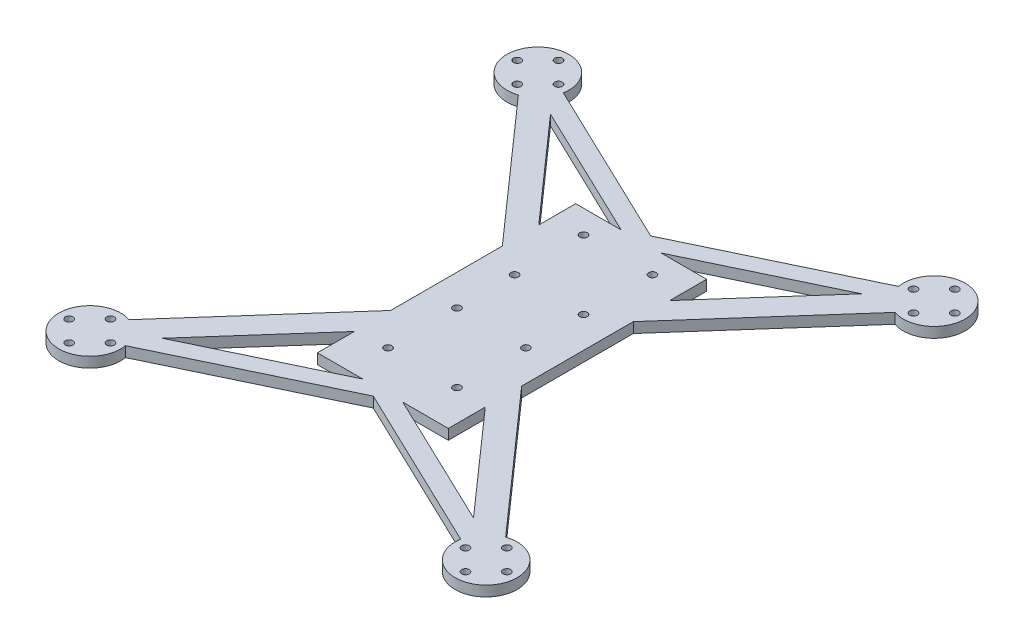
SolidWorks part; units mm, degrees
ref_plane "Front Plane" through (0, 0, 0) normal (0, 0, 1) x (1, 0, 0)
ref_plane "Top Plane" through (0, 0, 0) normal (0, 1, 0) x (1, 0, 0)
ref_plane "Right Plane" through (0, 0, 0) normal (1, 0, 0) x (0, 0, -1)
sketch "Sketch1" plane through (0, 0, 0) normal (0, 1, 0) x (1, 0, 0)
  line L0 (0, 37.475) -> (0, -37.475) construction
  line L1 (19, 37.475) -> (-19, 37.475)
  line L2 (19, 37.475) -> (19, -37.475)
  line L3 (19, -37.475) -> (-19, -37.475)
  line L4 (-19, 37.475) -> (-19, -37.475)
  line L5 (19, 37.475) -> (-19, -37.475) construction
  line L6 (19, -37.475) -> (-19, 37.475) construction
  line L7 (-19, 16.1958) -> (-54.6277, 56.4706)
  line L8 (57.5, -65) -> (-57.5, -65)
  line L9 (57.5, -65) -> (57.5, 65)
  line L10 (57.5, 65) -> (-57.5, 65)
  line L11 (-57.5, -65) -> (-57.5, 65)
  line L12 (57.5, -65) -> (-57.5, 65) construction
  line L13 (57.5, 65) -> (-57.5, -65) construction
  line L14 (-19, 16.1958) -> (-13.757, 20.8338)
  line L15 (-54.6277, 56.4706) -> (-49.3847, 61.1087)
  line L16 (-13.757, 20.8338) -> (-49.3847, 61.1087)
  line L17 (-19, 16.1958) -> (-49.3847, 61.1087) construction
  line L18 (-54.6277, 56.4706) -> (-13.757, 20.8338) construction
  line L19 (-57.5, 65) -> (0, 37.475) construction
  line L20 (-10, 30.75) -> (10, 30.75)
  line L21 (-10, 30.75) -> (-10, 10.75)
  line L22 (-10, 10.75) -> (10, 10.75)
  line L23 (10, 30.75) -> (10, 10.75)
  line L24 (-10, 30.75) -> (10, 10.75) construction
  line L25 (-10, 10.75) -> (10, 30.75) construction
  line L26 (-14.5, 5.525) -> (14.5, 5.525)
  line L27 (-14.5, 5.525) -> (-14.5, 35.975)
  line L28 (-14.5, 35.975) -> (14.5, 35.975)
  line L29 (14.5, 5.525) -> (14.5, 35.975)
  line L30 (-14.5, 5.525) -> (14.5, 35.975) construction
  line L31 (-14.5, 35.975) -> (14.5, 5.525) construction
  line L32 (-10, -5.975) -> (10, -5.975)
  line L33 (-10, -5.975) -> (-10, -25.975)
  line L34 (-10, -25.975) -> (10, -25.975)
  line L35 (10, -5.975) -> (10, -25.975)
  line L36 (-10, -5.975) -> (10, -25.975) construction
  line L37 (-10, -25.975) -> (10, -5.975) construction
  line L38 (-15.75, -35.975) -> (15.75, -35.975)
  line L39 (-15.75, -35.975) -> (-15.75, 4.025)
  line L40 (-15.75, 4.025) -> (15.75, 4.025)
  line L41 (15.75, -35.975) -> (15.75, 4.025)
  line L42 (-15.75, -35.975) -> (15.75, 4.025) construction
  line L43 (-15.75, 4.025) -> (15.75, -35.975) construction
  line L44 (-50.7811, 59.012) -> (3.6312, 32.9651)
  line L45 (-50.7811, 59.012) -> (-48.6222, 63.5219)
  line L46 (3.6312, 32.9651) -> (5.7901, 37.475)
  line L47 (-48.6222, 63.5219) -> (5.7901, 37.475)
  line L48 (-50.7811, 59.012) -> (5.7901, 37.475) construction
  line L49 (3.6312, 32.9651) -> (-48.6222, 63.5219) construction
  line L50 (50.7811, 59.012) -> (48.6222, 63.5219)
  line L51 (48.6222, 63.5219) -> (-5.7901, 37.475)
  line L52 (-3.6312, 32.9651) -> (-5.7901, 37.475)
  line L53 (50.7811, 59.012) -> (-3.6312, 32.9651)
  line L54 (19, 16.1958) -> (13.757, 20.8338)
  line L55 (13.757, 20.8338) -> (49.3847, 61.1087)
  line L56 (54.6277, 56.4706) -> (49.3847, 61.1087)
  line L57 (19, 16.1958) -> (54.6277, 56.4706)
  line L58 (-57.5, 0) -> (57.5, 0) construction
  line L64 (19, -16.1958) -> (13.757, -20.8338)
  line L65 (13.757, -20.8338) -> (49.3847, -61.1087)
  line L69 (50.7811, -59.012) -> (48.6222, -63.5219)
  line L70 (48.6222, -63.5219) -> (-5.7901, -37.475)
  line L71 (-3.6312, -32.9651) -> (-5.7901, -37.475)
  line L72 (50.7811, -59.012) -> (-3.6312, -32.9651)
  line L73 (-50.7811, -59.012) -> (-48.6222, -63.5219)
  line L74 (-48.6222, -63.5219) -> (5.7901, -37.475)
  line L75 (3.6312, -32.9651) -> (5.7901, -37.475)
  line L76 (-50.7811, -59.012) -> (3.6312, -32.9651)
  line L77 (54.6277, -56.4706) -> (49.3847, -61.1087)
  line L78 (19, -16.1958) -> (54.6277, -56.4706)
  line L79 (-19, -16.1958) -> (-13.757, -20.8338)
  line L80 (-13.757, -20.8338) -> (-49.3847, -61.1087)
  line L81 (-54.6277, -56.4706) -> (-49.3847, -61.1087)
  line L82 (-19, -16.1958) -> (-54.6277, -56.4706)
  circle A0 centre (-57.5, 65) radius 36
  circle A1 centre (-57.5, 65) radius 6
  circle A2 centre (-57.5, 65) radius 9
  circle A3 centre (-10, 30.75) radius 1.1
  circle A4 centre (10, 30.75) radius 1.1
  circle A5 centre (10, 10.75) radius 1.1
  circle A6 centre (-10, 10.75) radius 1.1
  circle A7 centre (-10, -5.975) radius 1.1
  circle A8 centre (10, -5.975) radius 1.1
  circle A9 centre (10, -25.975) radius 1.1
  circle A10 centre (-10, -25.975) radius 1.1
  circle A11 centre (-57.5, 71) radius 1.1
  circle A12 centre (-63.5, 65) radius 1.1
  circle A13 centre (-57.5, 59) radius 1.1
  circle A14 centre (-51.5, 65) radius 1.1
  circle A15 centre (57.5, 59) radius 1.1
  circle A16 centre (51.5, 65) radius 1.1
  circle A17 centre (57.5, 71) radius 1.1
  circle A18 centre (63.5, 65) radius 1.1
  circle A19 centre (57.5, 65) radius 9
  circle A20 centre (57.5, -65) radius 9
  circle A21 centre (51.5, -65) radius 1.1
  circle A22 centre (57.5, -59) radius 1.1
  circle A23 centre (63.5, -65) radius 1.1
  circle A24 centre (57.5, -71) radius 1.1
  circle A25 centre (-57.5, -59) radius 1.1
  circle A26 centre (-51.5, -65) radius 1.1
  circle A27 centre (-57.5, -71) radius 1.1
  circle A28 centre (-63.5, -65) radius 1.1
  circle A29 centre (-57.5, -65) radius 9
  circle A30 centre (-57.5, -65) radius 36
  circle A31 centre (57.5, 65) radius 36
  circle A32 centre (57.5, -65) radius 36
  point P0 (0, 0)
  point P8 (0, 0)
  point P16 (0, 20.75)
  point P18 (-34.1924, 38.6522)
  point P26 (0, 20.75)
  point P31 (0, -15.975)
  point P36 (0, -15.975)
  point P58 (-22.4955, 48.2435)
  point P102 (0, 0)
  point P103 (-34.1924, -38.6522)
  dimension "D3" = 72
  dimension "D4" = 12
  dimension "D5" = 3
  dimension "D17" = 2.2
  dimension "D2" = 1.5
  dimension "D6" = 115
  dimension "D7" = 130
  dimension "D8" = 3.25
  dimension "D9" = 7
  dimension "D10" = 20
  dimension "D11" = 29
  dimension "D12" = 30.45
  dimension "D13" = 40
  dimension "D14" = 31.5
  dimension "D15" = 1.5
  dimension "D16" = 1.5
  dimension "D18" = 5
extrude "Boss-Extrude1" add sketch "Sketch1" along normal blind 3 contours A2 | A11 | A14 | A13 | A12 | L7 L15 L16 L14 | L47 L46 L44 L45 | A19 | A15 | A18 | A17 | A16 | L57 L56 L55 L54 | L51 L52 L53 L50 | L1 L4 L3 L2 | A29 | A27 | A28 | A25 | A26 | L74 L75 L76 L73 | L80 L81 L82 L79 | A20 | A24 | A21 | A22 | A23 | L70 L71 L72 L69 | L65 L77 L78 L64 | A4 | A3 | A7 | A8 | A9 | A10 | A5 | A6
